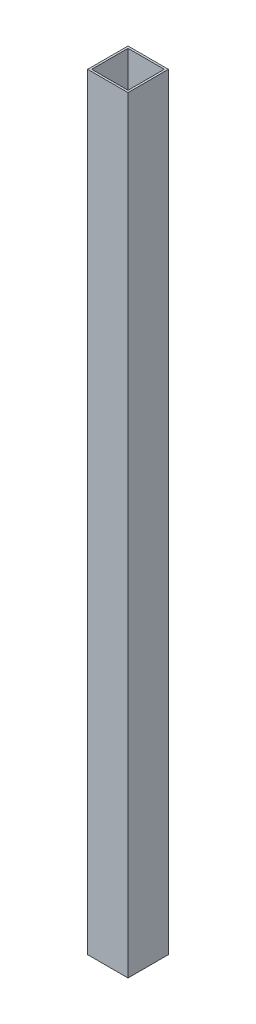
SolidWorks part; units mm, degrees
ref_plane "Front Plane" through (0, 0, 0) normal (0, 0, 1) x (1, 0, 0)
ref_plane "Top Plane" through (0, 0, 0) normal (0, 1, 0) x (1, 0, 0)
ref_plane "Right Plane" through (0, 0, 0) normal (1, 0, 0) x (0, 0, -1)
sketch "Sketch1" plane through (0, 0, 0) normal (0, 1, 0) x (1, 0, 0)
  line L0 (0, 0) -> (0, 25.4)
  line L1 (0, 25.4) -> (25.4, 25.4)
  line L2 (25.4, 25.4) -> (25.4, 0)
  line L3 (25.4, 0) -> (0, 0)
  line L6 (1.27, 12.3615) -> (1.27, 24.13)
  line L7 (1.27, 24.13) -> (12.7, 24.13)
  line L10 (12.7, 24.13) -> (24.13, 24.13)
  line L11 (24.13, 24.13) -> (24.13, 12.7)
  line L12 (24.13, 1.27) -> (24.13, 12.7)
  line L13 (24.13, 1.27) -> (12.7, 1.27)
  line L14 (1.27, 1.27) -> (12.7, 1.27)
  line L15 (1.27, 12.3615) -> (1.27, 1.27)
  dimension "D1" = 25.4
  dimension "D2" = 25.4
  dimension "D3" = 11.7685
  dimension "D4" = 11.0915
  dimension "D5" = 11.43
  dimension "D6" = 11.43
extrude "Boss-Extrude1" add sketch "Sketch1" along normal blind 482.6
